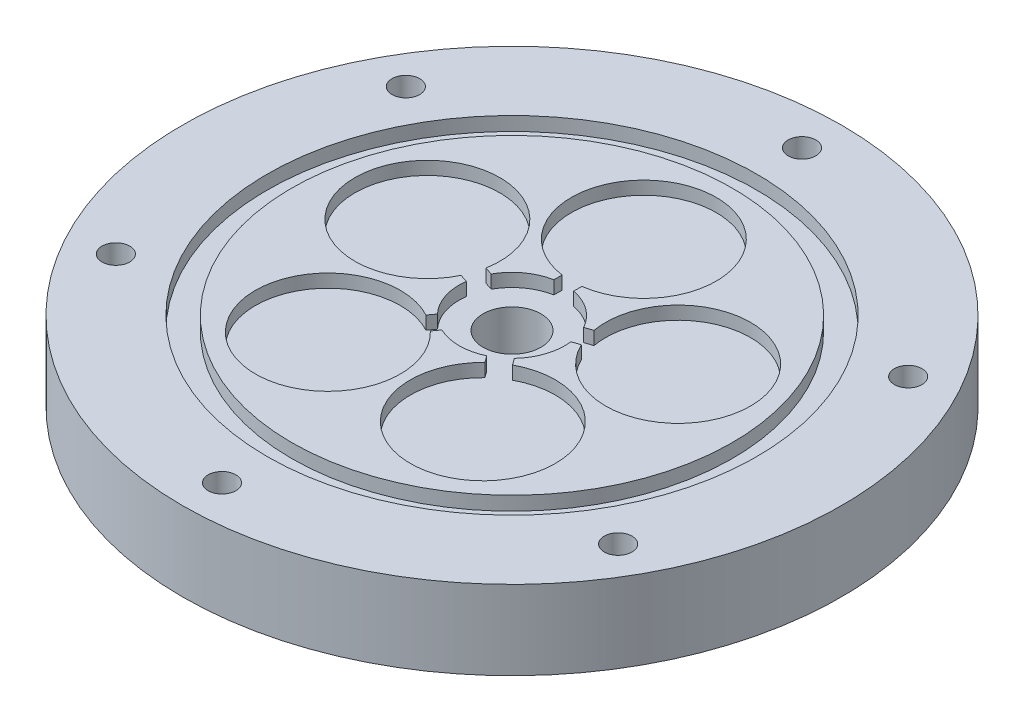
SolidWorks part; units mm, degrees
ref_plane "Alzado" through (0, 0, 0) normal (0, 0, 1) x (1, 0, 0)
ref_plane "Planta" through (0, 0, 0) normal (0, 1, 0) x (1, 0, 0)
ref_plane "Vista lateral" through (0, 0, 0) normal (1, 0, 0) x (0, 0, -1)
sketch "Croquis2" plane through (0, 0, 0) normal (0, 1, 0) x (1, 0, 0)
  circle A0 centre (0, 0) radius 50
  circle A2 centre (0, 0) radius 45 construction
  circle A3 centre (0, 0) radius 20 construction
  circle A4 centre (0, 20) radius 11
  circle A5 centre (0, 0) radius 44 construction
  circle A6 centre (0, 44) radius 2.5 construction
  circle A7 centre (0, 0) radius 35.285 construction
  circle A8 centre (0, 35.285) radius 1.31 construction
  circle A9 centre (0, 0) radius 8
  circle A10 centre (0, 0) radius 33.975 construction
  dimension "D1" = 22
  dimension "D2" = 40
  dimension "D3" = 100
  dimension "D4" = 90
  dimension "D5" = 5
  dimension "D6" = 6
  dimension "D7" = 2.62
  dimension "D8" = 67.95
  dimension "D9" = 16
extrude "Saliente-Extruir1" add sketch "Croquis2" against normal blind 12 contours A0
extrude "Cortar-Extruir1" cut sketch "Croquis2<3>" against normal blind 2 contours A4
sketch "Croquis2<3>" plane through (0, 0, 0) normal (0, 1, 0) x (1, 0, 0) same geometry as "Croquis2"
extrude "Cortar-Extruir4" cut sketch "Croquis2<6>" against normal up to surface (2 mm away) contours A9 up to face at (0, -2, -9)
sketch "Croquis2<6>" plane through (0, 0, 0) normal (0, 1, 0) x (1, 0, 0) same geometry as "Croquis2"
hole_wizard "Taladro roscado G1/81" positions "Croquis4" profile "Croquis5" tap size "G1/8" standard "GB" end condition through all
sketch "Croquis4" plane through (0, -12, 0) normal (0, -1, 0) x (-1, 0, 0)
  point P0 (0, 0)
sketch "Croquis5" plane through (0, -12, 0) normal (1, 0, 0) x (0, 0, -1)
  line L0 (0, 0) -> (0, 12)
  line L1 (0, 12) -> (4.4, 12)
  line L2 (4.4, 12) -> (4.4, 0)
  line L5 (4.4, 0) -> (0, 0)
  line L11 (0, -6.35) -> (0, 107.95) construction
  dimension "Diámetro de perforador para roscar hasta el siguiente" = 8.8
  dimension "Profundidad de perforador para roscar hasta el siguiente" = 12
cosmetic thread "Rosca de taladro1"
sketch "Croquis6" plane through (0, 0, 0) normal (0, 1, 0) x (1, 0, 0)
  line L0 (0, 20) -> (0, 0) construction
  line L1 (1.5, 20) -> (1.5, 0)
  line L2 (-1.5, 20) -> (-1.5, 0)
  arc A1 (1.5, 20) -> (-1.5, 20) centre (0, 20) ccw
  arc A2 (-1.5, 0) -> (1.5, 0) centre (0, 0) ccw
  point P6 (0, 10)
  dimension "D1" = 3
extrude "Cortar-Extruir3" cut sketch "Croquis6" against normal up to surface (2 mm away) up to face at (0, -2, -9)
pattern_circular "MatrizC1" count 5 over 360 about axis through (0, -12, 0) along (0, 1, 0) of "Cortar-Extruir3", "Cortar-Extruir1"
sketch "Croquis7" plane through (0, 0, 0) normal (1, 0, 0) x (0, 0, -1)
  line L1 (37.135, 2.1) -> (33.435, 2.1)
  line L2 (37.135, 2.1) -> (37.135, -2.1)
  line L3 (37.135, -2.1) -> (33.435, -2.1)
  line L4 (33.435, 2.1) -> (33.435, -2.1)
  line L5 (37.135, 2.1) -> (33.435, -2.1) construction
  line L6 (37.135, -2.1) -> (33.435, 2.1) construction
  line L9 (0, 0) -> (0, -28.3585) construction
  point P0 (35.285, 0)
  dimension "D1" = 4.2
  dimension "D2" = 3.7
revolve "Cortar-Revolución1" cut sketch "Croquis7" angle 360 about L9
hole_wizard "Taladro roscado M51" positions "Croquis8" profile "Croquis9" tap size "M5" standard "DIN" end condition through all
sketch "Croquis8" plane through (0, 0, 0) normal (0, 1, 0) x (1, 0, 0)
  point P0 (0, 44)
sketch "Croquis9" plane through (0, 0, -44) normal (1, 0, 0) x (0, 0, 1)
  line L0 (0, 0) -> (0, 12)
  line L1 (0, 12) -> (2.1, 12)
  line L2 (2.1, 12) -> (2.1, 0)
  line L5 (2.1, 0) -> (0, 0)
  line L11 (0, -6.35) -> (0, 107.95) construction
  dimension "Diámetro de perforador para roscar hasta el siguiente" = 4.2
  dimension "Profundidad de perforador para roscar hasta el siguiente" = 12
cosmetic thread "Rosca de taladro2"
pattern_circular "MatrizC2" count 6 over 360 about axis through (0, -12, 0) along (0, 1, 0) of "Taladro roscado M51" reverse direction yes
equation "\"D1@Croquis7\"=2.10*2"
